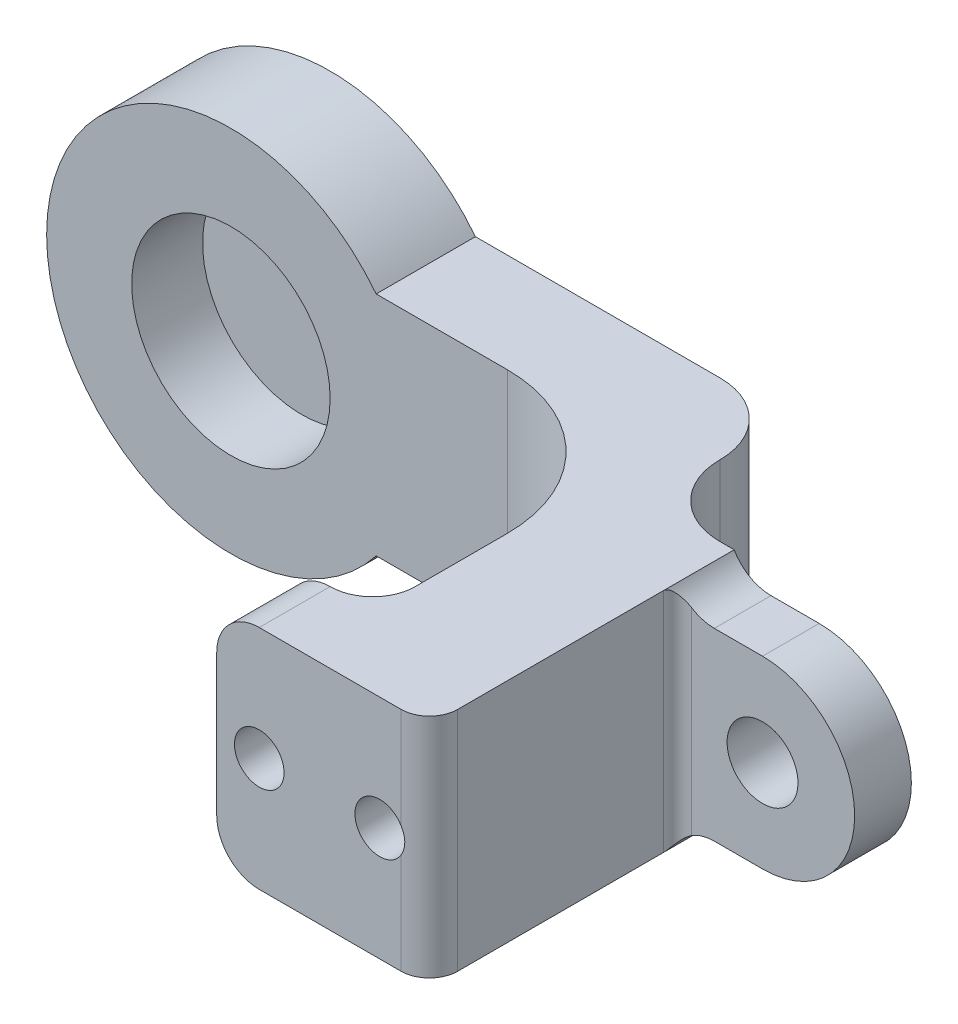
SolidWorks part; units mm, degrees
ref_plane "Front Plane" through (0, 0, 0) normal (0, 0, 1) x (1, 0, 0)
ref_plane "Top Plane" through (0, 0, 0) normal (0, 1, 0) x (1, 0, 0)
ref_plane "Right Plane" through (0, 0, 0) normal (1, 0, 0) x (0, 0, -1)
sketch "Sketch1" plane through (0, 0, 0) normal (0, 0, 1) x (1, 0, 0)
  line L1 (0, -8) -> (29.5, -8)
  line L2 (0, -8) -> (0, 8)
  line L3 (0, 8) -> (29.5, 8)
  line L4 (29.5, -8) -> (29.5, 8)
  arc A0 (0, -8) -> (0, 8) centre (0, 0) ccw
  circle A1 centre (0, 0) radius 13
  dimension "D1" = 16
  dimension "D2" = 5
  dimension "D3" = 29.5
extrude "Boss-Extrude1" add sketch "Sketch1" along normal blind 7 contours A1 L1 L4 L3 | L2 A0 | L1 A1 L3 A0 | L3 A1 L1 L2 region at (8.9868, 0, 0) region at (-3.5062, 0, 0) region at (3.3953, 0, 0) region at (20.7939, 0, 0)
sketch "Sketch3" plane through (0, 0, 7) normal (0, 0, 1) x (1, 0, 0)
  line L1 (29.5, 8) -> (32.5, 8)
  line L2 (29.5, 8) -> (29.5, -8)
  line L3 (29.5, -8) -> (32.5, -8)
  line L4 (32.5, 8) -> (32.5, -8)
  dimension "D1" = 3
extrude "Boss-Extrude3" add sketch "Sketch3" along normal blind 24.5 and the other way blind 7
sketch "Sketch4" plane through (29.5, 0, 0) normal (-1, 0, 0) x (0, 0, 1)
  line L0 (7, -8) -> (31.5, -8) construction
  line L1 (31.5, 8) -> (26.5, 8)
  line L2 (31.5, 8) -> (31.5, -8)
  line L3 (31.5, -8) -> (26.5, -8)
  line L4 (26.5, 8) -> (26.5, -8)
  dimension "D1" = 5
extrude "Boss-Extrude4" add sketch "Sketch4" along normal blind 6
sketch "Sketch5" plane through (32.5, 0, 0) normal (1, 0, 0) x (0, 0, -1)
  line L0 (0, -8) -> (-31.5, -8) construction
  line L1 (-31.5, 8) -> (-10, 8)
  line L2 (-31.5, 8) -> (-31.5, -8)
  line L3 (-31.5, -8) -> (-10, -8)
  line L4 (-10, 8) -> (-10, -8)
  dimension "D1" = 21.5
extrude "Boss-Extrude5" add sketch "Sketch5" along normal blind 6
sketch "Sketch6" plane through (0, 0, 7) normal (0, 0, 1) x (1, 0, 0)
  circle A0 centre (0, 0) radius 7
  dimension "D1" = 14
extrude "Cut-Extrude1" cut sketch "Sketch6" against normal blind 5
sketch "Sketch8" plane through (0, 0, 26.5) normal (0, 0, -1) x (-1, 0, 0)
  line L0 (-29.5, 8) -> (-29.5, -8) construction
  line L1 (-23.5, 8) -> (-29.5, 8) construction
  circle A0 centre (-26.5, 0) radius 1.75
  dimension "D1" = 3
  dimension "D2" = 3.5
  dimension "D3" = 8
extrude "Cut-Extrude2" cut sketch "Sketch8" against normal blind 5
sketch "Sketch10" plane through (0, 0, 10) normal (0, 0, -1) x (-1, 0, 0)
  line L0 (-38.5, 8) -> (-32.5, 8) construction
  line L1 (-44.5, 6.498) -> (-38.5, 6.498)
  line L2 (-38.5, -8) -> (-38.5, 8) construction
  line L3 (-38.5, -8) -> (-38.5, 8)
  line L5 (-38.5, 6.498) -> (-38.5, -6.502)
  line L6 (-38.5, -6.502) -> (-44.5, -6.502)
  circle A0 centre (-44.5, -0.002) radius 2.5
  arc A1 (-44.5, 6.498) -> (-44.5, -6.502) centre (-44.5, -0.002) ccw
  line M5 (-38.5, 8) -> (-38.5, -8)
  dimension "D1" = 5
  dimension "D2" = 4
  dimension "D3" = 6
  dimension "D4" = 8.002
extrude "Boss-Extrude6" add sketch "Sketch10" against normal blind 4 contours A1 A0 | A1 M5 | A1 M5 region at (41.5, 6.3176, 10)
sketch "Sketch11" plane through (0, 0, 10) normal (0, 0, -1) x (-1, 0, 0)
  line L0 (-32.5, -8) -> (-32.5, 8) construction
  circle A0 centre (-35, 0) radius 1.75
  dimension "D1" = 3.5
  dimension "D2" = 2.5
extrude "Cut-Extrude4" cut sketch "Sketch11" against normal blind 32
fillet "Fillet2" radius 2 1 edges at (38.5, 0, 31.5)
fillet "Fillet3" radius 3 2 edges at (23.5, -8, 29) (23.5, 8, 29)
fillet "Fillet5" radius 1 1 edges at (38.5, -0.002, 14)
fillet "Fillet7" radius 3 1 edges at (29.5, 0, 26.5)
fillet "Fillet8" radius 10 1 edges at (29.5, 0, 7)
fillet "Fillet10" radius 3 2 edges at (38.5, 6.498, 12.5) (38.5, -6.502, 12.5)
fillet "Fillet11" radius 5 2 edges at (32.5, 0, 0) (32.5, 0, 10)
